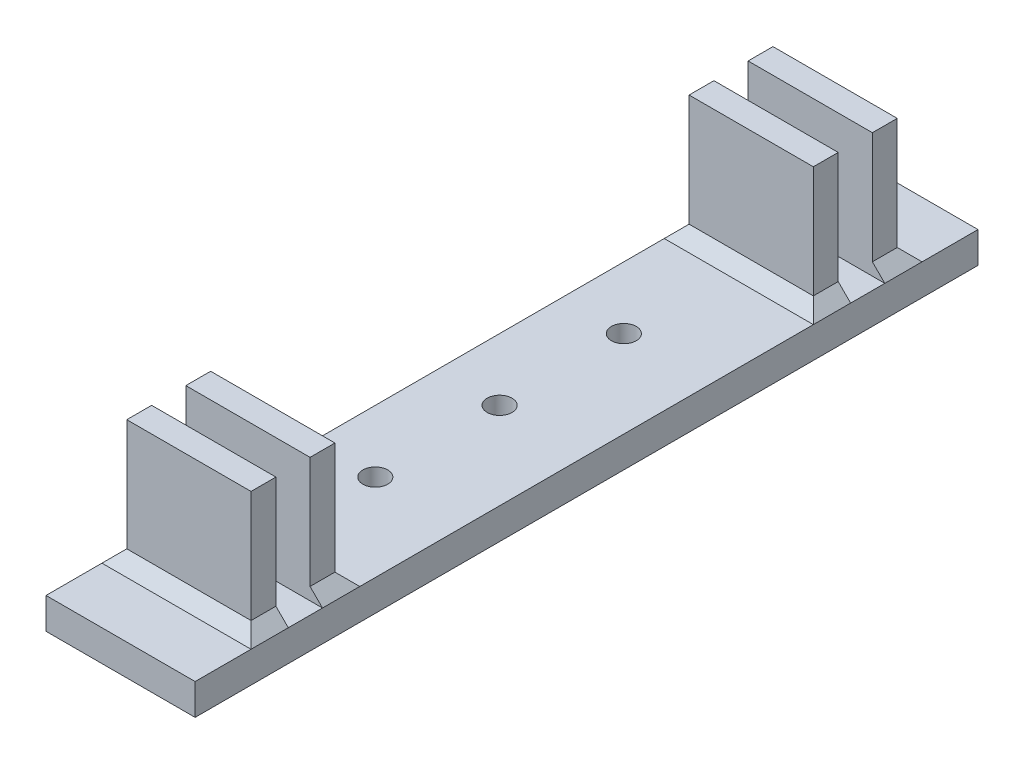
SolidWorks part; units mm, degrees
ref_plane "Front Plane" through (0, 0, 0) normal (0, 0, 1) x (1, 0, 0)
ref_plane "Top Plane" through (0, 0, 0) normal (0, 1, 0) x (1, 0, 0)
ref_plane "Right Plane" through (0, 0, 0) normal (1, 0, 0) x (0, 0, -1)
sketch "Sketch1" plane through (0, 0, 0) normal (0, 1, 0) x (1, 0, 0)
  line L1 (-74.6509, 30.6509) -> (-50.6509, 30.6509)
  line L2 (-74.6509, 30.6509) -> (-74.6509, -95.3491)
  line L3 (-74.6509, -95.3491) -> (-50.6509, -95.3491)
  line L4 (-50.6509, 30.6509) -> (-50.6509, -95.3491)
  dimension "D1" = 24
  dimension "D2" = 126
extrude "Boss-Extrude1" add sketch "Sketch1" along normal blind 5
sketch "Sketch2" plane through (0, 5, 0) normal (0, 1, 0) x (1, 0, 0)
  line L0 (-50.6509, -95.3491) -> (-50.6509, 30.6509) construction
  line L6 (-74.6509, 30.6509) -> (-74.6509, -95.3491) construction
  line L7 (-74.6509, -32.3491) -> (-50.6509, -32.3491) construction
  line L8 (-72.6509, 15.6509) -> (-52.6509, 15.6509)
  line L13 (-151.7654, 10.6509) -> (-50.6509, 10.6509) construction
  line L15 (-72.6509, 15.6509) -> (-72.6509, 19.6509)
  line L16 (-72.6509, 19.6509) -> (-52.6509, 19.6509)
  line L17 (-52.6509, 15.6509) -> (-52.6509, 19.6509)
  line L18 (-72.6509, 6.1509) -> (-52.6509, 6.1509)
  line L19 (-72.6509, 6.1509) -> (-72.6509, 10.1509)
  line L20 (-72.6509, 10.1509) -> (-52.6509, 10.1509)
  line L21 (-52.6509, 6.1509) -> (-52.6509, 10.1509)
  line L22 (-52.6509, -70.8491) -> (-52.6509, -74.8491)
  line L23 (-72.6509, -74.8491) -> (-52.6509, -74.8491)
  line L24 (-72.6509, -70.8491) -> (-72.6509, -74.8491)
  line L25 (-72.6509, -70.8491) -> (-52.6509, -70.8491)
  line L26 (-52.6509, -80.3491) -> (-52.6509, -84.3491)
  line L27 (-72.6509, -84.3491) -> (-52.6509, -84.3491)
  line L28 (-72.6509, -80.3491) -> (-72.6509, -84.3491)
  line L29 (-52.6509, -80.3491) -> (-72.6509, -80.3491)
  line L30 (-62.6509, 30.6509) -> (-62.6509, -95.3491) construction
  line L31 (-50.6509, 30.6509) -> (-74.6509, 30.6509) construction
  line L32 (-74.6509, -95.3491) -> (-50.6509, -95.3491) construction
  dimension "D2" = 4
  dimension "D3" = 0.5
  dimension "D1" = 4
  dimension "D4" = 10
  dimension "D5" = 10
  dimension "D6" = 20
  dimension "D7" = 10
extrude "Boss-Extrude2" add sketch "Sketch2" along normal blind 20
sketch "Sketch3" plane through (0, 5, 0) normal (0, 1, 0) x (1, 0, 0)
  line L0 (-64.6509, 30.6509) -> (-64.6509, -95.3491) construction
  line L1 (-50.6509, 30.6509) -> (-74.6509, 30.6509) construction
  line L2 (-74.6509, -95.3491) -> (-50.6509, -95.3491) construction
  line L3 (-50.6509, -95.3491) -> (-50.6509, 30.6509) construction
  line L4 (-64.6509, -32.3491) -> (13.4519, -32.3491) construction
  circle A0 centre (-64.6509, -32.3491) radius 2
  circle A1 centre (-64.6509, -12.3491) radius 2
  circle A2 centre (-64.6509, -52.3491) radius 2
  dimension "D1" = 4
  dimension "D3" = 4
  dimension "D2" = 14
  dimension "D4" = 20
extrude "Cut-Extrude1" cut sketch "Sketch3" against normal through all both and the other way through all
chamfer "Chamfer1" distance 2 angle 45 12 edges at (-72.6509, 5, 72.8491) (-62.6509, 5, 70.8491) (-52.6509, 5, 72.8491) (-72.6509, 5, 82.3491) (-62.6509, 5, 84.3491) (-52.6509, 5, 82.3491) (-72.6509, 5, -17.6509) (-62.6509, 5, -19.6509) (-52.6509, 5, -17.6509) (-72.6509, 5, -8.1509) (-62.6509, 5, -6.1509) (-52.6509, 5, -8.1509)
